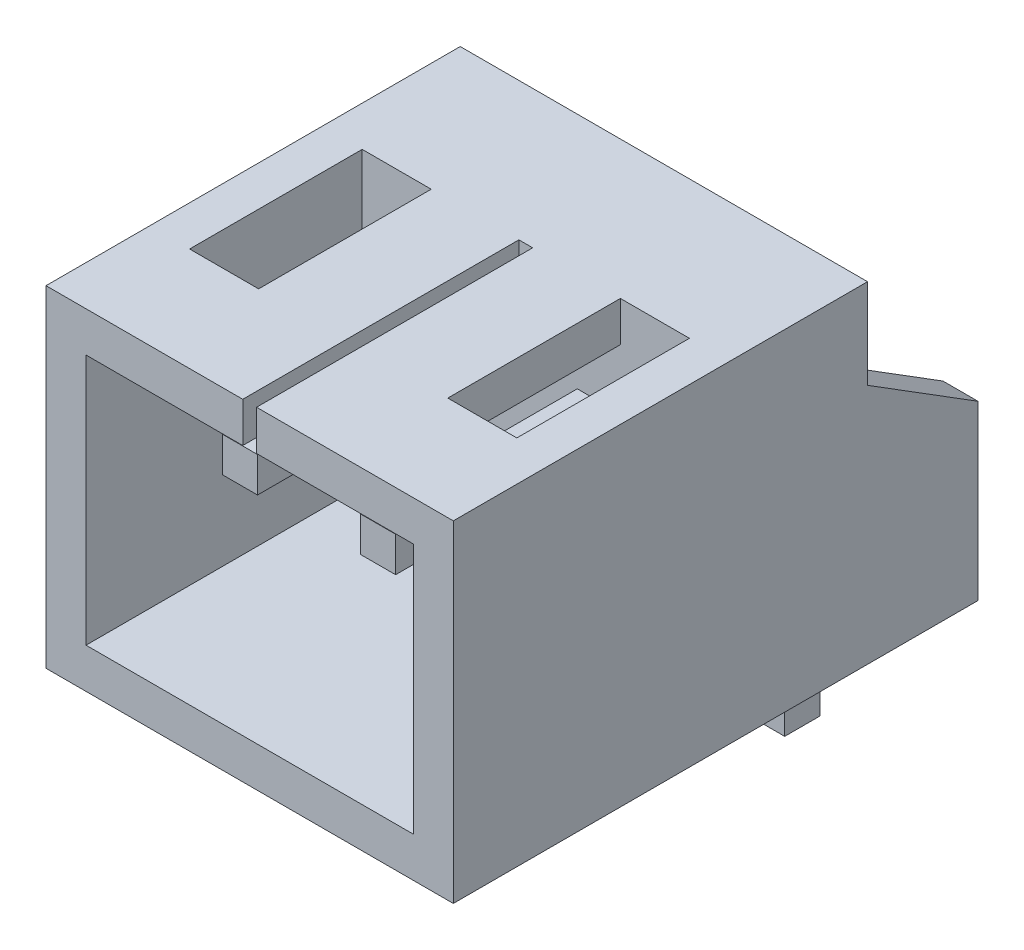
SolidWorks part; units mm, degrees
material "A-Glass Fiber"
ref_plane "Front Plane" through (0, 0, 0) normal (0, 0, 1) x (1, 0, 0)
ref_plane "Top Plane" through (0, 0, 0) normal (0, 1, 0) x (1, 0, 0)
ref_plane "Right Plane" through (0, 0, 0) normal (1, 0, 0) x (0, 0, -1)
sketch "Sketch4" plane through (6.8642, -1.8637, 0) normal (0, 0, 1) x (1, 0, 0)
  line L0 (-9.8142, 4.2637) -> (-3.9142, -0.5363) construction
  line L7 (-3.9142, 4.2637) -> (-9.8142, 4.2637)
  line L8 (-3.9142, 4.2637) -> (-3.9142, -0.5363)
  line L9 (-3.9142, -0.5363) -> (-9.8142, -0.5363)
  line L10 (-9.8142, 4.2637) -> (-9.8142, -0.5363)
  dimension "D4" = 5.9
  dimension "D7" = 4.8
extrude "Body-Extrude2" add sketch "Sketch4" along normal blind 6 separate body
shell "Body-Shell1" thickness 0.58 removed face at (0, 0, 6)
sketch "Sketch66" plane through (0, 1.82, 0) normal (0, 1, 0) x (1, 0, 0)
  line L1 (0.1, -6) -> (-0.1, -6)
  line L2 (0.1, -6) -> (0.1, -2)
  line L3 (0.1, -2) -> (-0.1, -2)
  line L4 (-0.1, -6) -> (-0.1, -2)
  line L7 (-1.37, -2) -> (-2.37, -2)
  line L8 (-1.37, -2) -> (-1.37, -4.5)
  line L9 (-1.37, -4.5) -> (-2.37, -4.5)
  line L10 (-2.37, -2) -> (-2.37, -4.5)
  line L13 (1.37, -2) -> (2.37, -2)
  line L14 (1.37, -2) -> (1.37, -4.5)
  line L15 (1.37, -4.5) -> (2.37, -4.5)
  line L16 (2.37, -2) -> (2.37, -4.5)
  line L17 (-2.37, -2) -> (2.37, -2) construction
  line L18 (-2.37, -6) -> (-2.37, -2) construction
  line L19 (2.37, -6) -> (2.37, -2) construction
  line L20 (-2.37, -6) -> (2.37, -6) construction
  line L21 (2.95, -6) -> (2.95, 0) construction
  point P7 (0, -2)
  dimension "D1" = 2.85
  dimension "D2" = 2.5
  dimension "D3" = 1
extrude "Extrude1" cut sketch "Sketch66" along normal up to next
sketch "Sketch6" plane through (2.95, 11.1173, 0) normal (1, 0, 0) x (0, 0, -1)
  line L0 (0, -10.0173) -> (1.6, -11.0173)
  line L1 (0, -13.5173) -> (0, -8.7173) construction
  line L2 (1.6, -11.0173) -> (1.6, -13.5173)
  line L3 (0, -13.5173) -> (1.6, -13.5173)
  line L4 (0, -10.0173) -> (0, -13.5173)
  line L5 (-6, -13.5173) -> (0, -13.5173) construction
  line L6 (-6, -8.7173) -> (0, -8.7173) construction
  dimension "D1" = 1.3
  dimension "D2" = 1.6
  dimension "D3" = 2.5
extrude "Tab-Extrude4" add sketch "Sketch6" against normal blind 0.508
sketch "Sketch9" plane through (-2.95, 11.1173, 0) normal (-1, 0, 0) x (0, 0, 1)
  line L4 (0, -13.5173) -> (0, -10.0173)
  line L5 (0, -13.5173) -> (0, -10.0173)
  line L7 (0, -10.0173) -> (-1.6, -11.0173)
  line L8 (-1.6, -11.0173) -> (-1.6, -13.5173)
  line L9 (-1.6, -13.5173) -> (0, -13.5173)
  line L11 (0, -10.0173) -> (-1.6, -11.0173)
  line L12 (-1.6, -11.0173) -> (-1.6, -13.5173)
  line L15 (-1.6, -13.5173) -> (0, -13.5173)
  dimension "D1" = 0
extrude "Tab-Extrude7" add sketch "Sketch9" against normal blind 0.508
ref_plane "Pins-Plane" through (0, 0, 5.14) normal (0, 0, 1) x (1, 0, 0)
sketch "Sketch64" plane through (0, 3.64, 5.14) normal (0, 0, -1) x (1, 0, 0)
  line L1 (-1.254, 3.194) -> (-0.746, 3.194)
  line L2 (-1.254, 3.194) -> (-1.254, 2.686)
  line L3 (-1.254, 2.686) -> (-0.746, 2.686)
  line L4 (-0.746, 3.194) -> (-0.746, 2.686)
  line L5 (-2.95, 1.24) -> (-2.95, 6.04) construction
  line L6 (2.95, 1.24) -> (0.1, 1.24) construction
  line L11 (-1.254, 3.194) -> (-0.746, 2.686) construction
  line L15 (-0.746, 2.94) -> (0, 2.94) construction
  point P8 (-1, 2.94)
  dimension "D1" = 1.7
  dimension "D2" = 0.508
  dimension "D3" = 1.95
sketch "Sketch65" plane through (0, 0, 0) normal (1, 0, 0) x (0, 0, -1)
  line L0 (-5.14, 0.7) -> (-0.25, 0.7)
  line L1 (0.75, -0.3) -> (0.75, -4.4)
  line L2 (0, 1.1) -> (0, 2.4) construction
  line L3 (-6, -2.4) -> (1.6, -2.4) construction
  arc A0 (-0.25, 0.7) -> (0.75, -0.3) centre (-0.25, -0.3) cw
  dimension "D3" = 1
  dimension "D1" = 0.75
  dimension "D2" = 2
sweep "Pins-Sweep" add profiles "Sketch64" path "Sketch65"
ref_point "Point1"
ref_axis "Axis1" through (-1, -5.3906, -0.75) along (0, 1, 0)
pattern_linear "Pins-LPattern" count 2 spacing 2 along (1, 0, 0) of "Pins-Sweep"
